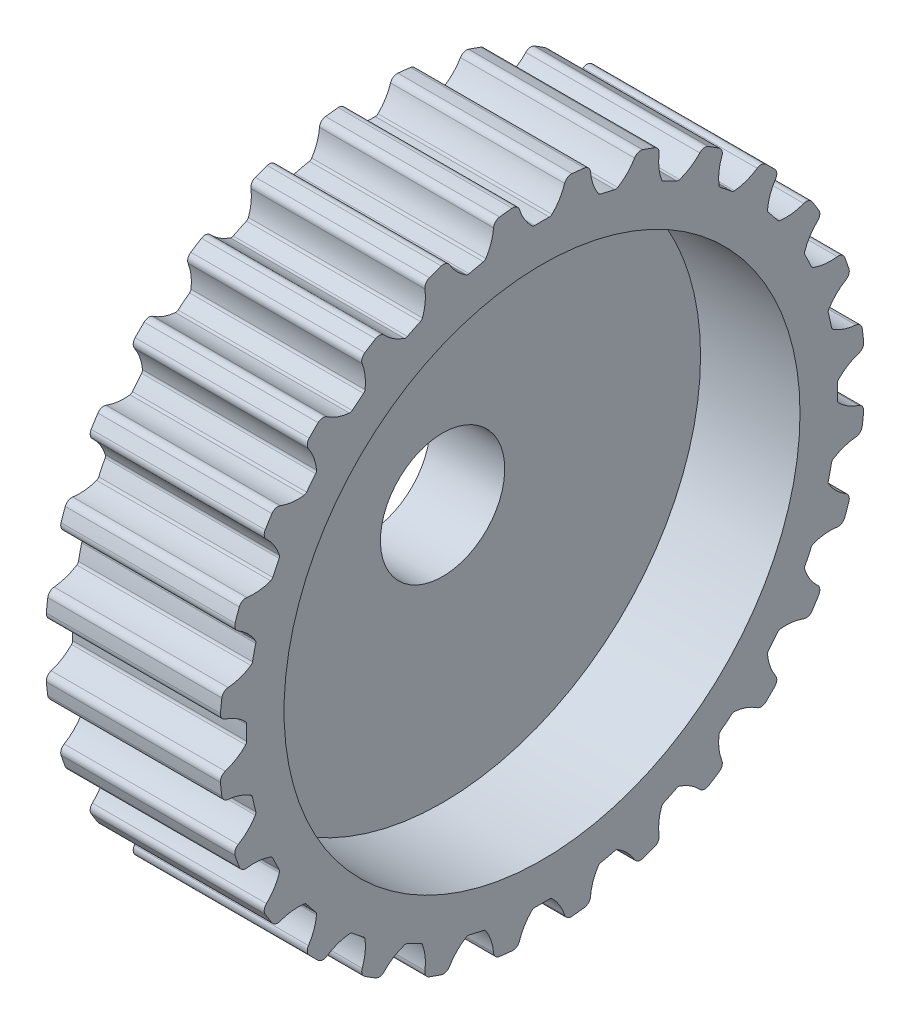
SolidWorks part; units mm, degrees
ref_plane "前视基准面" through (0, 0, 0) normal (0, 0, 1) x (1, 0, 0)
ref_plane "上视基准面" through (0, 0, 0) normal (0, 1, 0) x (1, 0, 0)
ref_plane "右视基准面" through (0, 0, 0) normal (1, 0, 0) x (0, 0, -1)
ref_plane "基准面1" through (0, 0, 0) normal (0, 0, 1) x (1, 0, 0)
sketch "草图1" plane through (0, 0, 0) normal (0, 0, 1) x (1, 0, 0)
  line L0 (0, 0) -> (0, 10)
  line L1 (0, 10) -> (1, 10)
  line L2 (1, 10) -> (1, 12.8583)
  line L3 (1, 12.8583) -> (0.4955, 14.7412)
  line L4 (0.4955, 14.7412) -> (1.4614, 15)
  line L5 (1.4614, 15) -> (2, 12.99)
  line L6 (2, 12.99) -> (9, 12.99)
  line L7 (9, 12.99) -> (9.5386, 15)
  line L8 (9.5386, 15) -> (10.5045, 14.7412)
  line L9 (10.5045, 14.7412) -> (10, 12.8583)
  line L10 (10, 12.8583) -> (10, 10)
  line L11 (10, 10) -> (11, 10)
  line L12 (11, 10) -> (11, 0)
  line L13 (11, 0) -> (0, 0)
  line L14 (11, 0) -> (0, 0) construction
revolve "旋转1" add sketch "草图1" angle 360 about L14 reverse direction yes
ref_plane "基准面2" through (0, 0, 0) normal (0, 0, 1) x (1, 0, 0)
hole_wizard "孔1" positions "草图3" profile "草图2" legacy
sketch "草图3" plane through (11, 0, 0) normal (1, 0, 0) x (0, 0, -1)
  point P0 (0, 0)
sketch "草图2" plane through (11, 0, 0) normal (0, 1, 0) x (0, 0, -1)
  line L0 (0, 0) -> (0, 11)
  line L1 (0, 11) -> (2.5, 11)
  line L2 (2.5, 11) -> (2.5, 0)
  line L3 (2.5, 0) -> (0, 0)
  line L4 (0, 110) -> (0, -10) construction
  dimension "直径" = 5
  dimension "深度" = 11
ref_plane "基准面3" through (2, 0, 0) normal (1, 0, 0) x (0, 0, -1)
sketch "草图4" plane through (2, 0, 0) normal (1, 0, 0) x (0, 0, -1)
  circle A0 centre (0, 0) radius 17.99
  arc A1 (-12.9343, 1.2013) -> (-12.7398, 0.9084) centre (-12.6555, 1.1754) ccw
  arc A2 (-12.7398, 0.9084) -> (-11.9188, 0.4022) centre (-13.3344, -0.975) cw
  arc A3 (-11.9188, 0.4022) -> (-11.8764, 0.2939) centre (-12.0263, 0.2976) cw
  arc A4 (-11.8764, 0.2939) -> (-11.8764, -0.2939) centre (0, 0) ccw
  arc A5 (-11.8764, -0.2939) -> (-11.9188, -0.4022) centre (-12.0263, -0.2976) cw
  arc A6 (-11.9188, -0.4022) -> (-12.7398, -0.9084) centre (-13.3344, 0.975) cw
  arc A7 (-12.7398, -0.9084) -> (-12.9343, -1.2013) centre (-12.6555, -1.1754) ccw
  arc A8 (-12.9343, -1.2013) -> (-12.8774, -1.707) centre (0, 0) ccw
  arc A9 (-12.8774, -1.707) -> (-12.6225, -1.9493) centre (-12.5998, -1.6702) ccw
  arc A10 (-12.6225, -1.9493) -> (-11.7095, -2.2601) centre (-12.7831, -3.9177) cw
  arc A11 (-11.7095, -2.2601) -> (-11.644, -2.3562) centre (-11.791, -2.386) cw
  arc A12 (-11.644, -2.3562) -> (-11.5132, -2.9293) centre (0, 0) ccw
  arc A13 (-11.5132, -2.9293) -> (-11.5305, -3.0443) centre (-11.6586, -2.9663) cw
  arc A14 (-11.5305, -3.0443) -> (-12.2183, -3.7205) centre (-13.217, -2.0166) cw
  arc A15 (-12.2183, -3.7205) -> (-12.3427, -4.0493) centre (-12.0767, -3.962) ccw
  arc A16 (-12.3427, -4.0493) -> (-12.1746, -4.5297) centre (0, 0) ccw
  arc A17 (-12.1746, -4.5297) -> (-11.8723, -4.7092) centre (-11.9122, -4.432) ccw
  arc A18 (-11.8723, -4.7092) -> (-10.913, -4.809) centre (-11.5908, -6.664) cw
  arc A19 (-10.913, -4.809) -> (-10.8278, -4.8882) centre (-10.9645, -4.9499) cw
  arc A20 (-10.8278, -4.8882) -> (-10.5727, -5.4178) centre (0, 0) ccw
  arc A21 (-10.5727, -5.4178) -> (-10.564, -5.5338) centre (-10.7062, -5.4862) cw
  arc A22 (-10.564, -5.5338) -> (-11.0841, -6.346) centre (-12.4369, -4.9071) cw
  arc A23 (-11.0841, -6.346) -> (-11.1322, -6.6943) centre (-10.8923, -6.55) ccw
  arc A24 (-11.1322, -6.6943) -> (-10.8615, -7.1252) centre (0, 0) ccw
  arc A25 (-10.8615, -7.1252) -> (-10.5268, -7.233) centre (-10.6273, -6.9716) ccw
  arc A26 (-10.5268, -7.233) -> (-9.5693, -7.1168) centre (-9.8174, -9.0761) cw
  arc A27 (-9.5693, -7.1168) -> (-9.4686, -7.175) centre (-9.5881, -7.2656) cw
  arc A28 (-9.4686, -7.175) -> (-9.1021, -7.6346) centre (0, 0) ccw
  arc A29 (-9.1021, -7.6346) -> (-9.0677, -7.7457) centre (-9.217, -7.731) cw
  arc A30 (-9.0677, -7.7457) -> (-9.394, -8.6534) centre (-11.0332, -7.5516) cw
  arc A31 (-9.394, -8.6534) -> (-9.3635, -9.0036) centre (-9.1617, -8.8096) ccw
  arc A32 (-9.3635, -9.0036) -> (-9.0036, -9.3635) centre (0, 0) ccw
  arc A33 (-9.0036, -9.3635) -> (-8.6534, -9.394) centre (-8.8096, -9.1617) ccw
  arc A34 (-8.6534, -9.394) -> (-7.7457, -9.0677) centre (-7.5516, -11.0332) cw
  arc A35 (-7.7457, -9.0677) -> (-7.6346, -9.1021) centre (-7.731, -9.217) cw
  arc A36 (-7.6346, -9.1021) -> (-7.175, -9.4686) centre (0, 0) ccw
  arc A37 (-7.175, -9.4686) -> (-7.1168, -9.5693) centre (-7.2656, -9.5881) cw
  arc A38 (-7.1168, -9.5693) -> (-7.233, -10.5268) centre (-9.0761, -9.8174) cw
  arc A39 (-7.233, -10.5268) -> (-7.1252, -10.8615) centre (-6.9716, -10.6273) ccw
  arc A40 (-7.1252, -10.8615) -> (-6.6943, -11.1322) centre (0, 0) ccw
  arc A41 (-6.6943, -11.1322) -> (-6.346, -11.0841) centre (-6.55, -10.8923) ccw
  arc A42 (-6.346, -11.0841) -> (-5.5338, -10.564) centre (-4.9071, -12.4369) cw
  arc A43 (-5.5338, -10.564) -> (-5.4178, -10.5727) centre (-5.4862, -10.7062) cw
  arc A44 (-5.4178, -10.5727) -> (-4.8882, -10.8278) centre (0, 0) ccw
  arc A45 (-4.8882, -10.8278) -> (-4.809, -10.913) centre (-4.9499, -10.9645) cw
  arc A46 (-4.809, -10.913) -> (-4.7092, -11.8723) centre (-6.664, -11.5908) cw
  arc A47 (-4.7092, -11.8723) -> (-4.5297, -12.1746) centre (-4.432, -11.9122) ccw
  arc A48 (-4.5297, -12.1746) -> (-4.0493, -12.3427) centre (0, 0) ccw
  arc A49 (-4.0493, -12.3427) -> (-3.7205, -12.2183) centre (-3.962, -12.0767) ccw
  arc A50 (-3.7205, -12.2183) -> (-3.0443, -11.5305) centre (-2.0166, -13.217) cw
  arc A51 (-3.0443, -11.5305) -> (-2.9293, -11.5132) centre (-2.9663, -11.6586) cw
  arc A52 (-2.9293, -11.5132) -> (-2.3562, -11.644) centre (0, 0) ccw
  arc A53 (-2.3562, -11.644) -> (-2.2601, -11.7095) centre (-2.386, -11.791) cw
  arc A54 (-2.2601, -11.7095) -> (-1.9493, -12.6225) centre (-3.9177, -12.7831) cw
  arc A55 (-1.9493, -12.6225) -> (-1.707, -12.8774) centre (-1.6702, -12.5998) ccw
  arc A56 (-1.707, -12.8774) -> (-1.2013, -12.9343) centre (0, 0) ccw
  arc A57 (-1.2013, -12.9343) -> (-0.9084, -12.7398) centre (-1.1754, -12.6555) ccw
  arc A58 (-0.9084, -12.7398) -> (-0.4022, -11.9188) centre (0.975, -13.3344) cw
  arc A59 (-0.4022, -11.9188) -> (-0.2939, -11.8764) centre (-0.2976, -12.0263) cw
  arc A60 (-0.2939, -11.8764) -> (0.2939, -11.8764) centre (0, 0) ccw
  arc A61 (0.2939, -11.8764) -> (0.4022, -11.9188) centre (0.2976, -12.0263) cw
  arc A62 (0.4022, -11.9188) -> (0.9084, -12.7398) centre (-0.975, -13.3344) cw
  arc A63 (0.9084, -12.7398) -> (1.2013, -12.9343) centre (1.1754, -12.6555) ccw
  arc A64 (1.2013, -12.9343) -> (1.707, -12.8774) centre (0, 0) ccw
  arc A65 (1.707, -12.8774) -> (1.9493, -12.6225) centre (1.6702, -12.5998) ccw
  arc A66 (1.9493, -12.6225) -> (2.2601, -11.7095) centre (3.9177, -12.7831) cw
  arc A67 (2.2601, -11.7095) -> (2.3562, -11.644) centre (2.386, -11.791) cw
  arc A68 (2.3562, -11.644) -> (2.9293, -11.5132) centre (0, 0) ccw
  arc A69 (2.9293, -11.5132) -> (3.0443, -11.5305) centre (2.9663, -11.6586) cw
  arc A70 (3.0443, -11.5305) -> (3.7205, -12.2183) centre (2.0166, -13.217) cw
  arc A71 (3.7205, -12.2183) -> (4.0493, -12.3427) centre (3.962, -12.0767) ccw
  arc A72 (4.0493, -12.3427) -> (4.5297, -12.1746) centre (0, 0) ccw
  arc A73 (4.5297, -12.1746) -> (4.7092, -11.8723) centre (4.432, -11.9122) ccw
  arc A74 (4.7092, -11.8723) -> (4.809, -10.913) centre (6.664, -11.5908) cw
  arc A75 (4.809, -10.913) -> (4.8882, -10.8278) centre (4.9499, -10.9645) cw
  arc A76 (4.8882, -10.8278) -> (5.4178, -10.5727) centre (0, 0) ccw
  arc A77 (5.4178, -10.5727) -> (5.5338, -10.564) centre (5.4862, -10.7062) cw
  arc A78 (5.5338, -10.564) -> (6.346, -11.0841) centre (4.9071, -12.4369) cw
  arc A79 (6.346, -11.0841) -> (6.6943, -11.1322) centre (6.55, -10.8923) ccw
  arc A80 (6.6943, -11.1322) -> (7.1252, -10.8615) centre (0, 0) ccw
  arc A81 (7.1252, -10.8615) -> (7.233, -10.5268) centre (6.9716, -10.6273) ccw
  arc A82 (7.233, -10.5268) -> (7.1168, -9.5693) centre (9.0761, -9.8174) cw
  arc A83 (7.1168, -9.5693) -> (7.175, -9.4686) centre (7.2656, -9.5881) cw
  arc A84 (7.175, -9.4686) -> (7.6346, -9.1021) centre (0, 0) ccw
  arc A85 (7.6346, -9.1021) -> (7.7457, -9.0677) centre (7.731, -9.217) cw
  arc A86 (7.7457, -9.0677) -> (8.6534, -9.394) centre (7.5516, -11.0332) cw
  arc A87 (8.6534, -9.394) -> (9.0036, -9.3635) centre (8.8096, -9.1617) ccw
  arc A88 (9.0036, -9.3635) -> (9.3635, -9.0036) centre (0, 0) ccw
  arc A89 (9.3635, -9.0036) -> (9.394, -8.6534) centre (9.1617, -8.8096) ccw
  arc A90 (9.394, -8.6534) -> (9.0677, -7.7457) centre (11.0332, -7.5516) cw
  arc A91 (9.0677, -7.7457) -> (9.1021, -7.6346) centre (9.217, -7.731) cw
  arc A92 (9.1021, -7.6346) -> (9.4686, -7.175) centre (0, 0) ccw
  arc A93 (9.4686, -7.175) -> (9.5693, -7.1168) centre (9.5881, -7.2656) cw
  arc A94 (9.5693, -7.1168) -> (10.5268, -7.233) centre (9.8174, -9.0761) cw
  arc A95 (10.5268, -7.233) -> (10.8615, -7.1252) centre (10.6273, -6.9716) ccw
  arc A96 (10.8615, -7.1252) -> (11.1322, -6.6943) centre (0, 0) ccw
  arc A97 (11.1322, -6.6943) -> (11.0841, -6.346) centre (10.8923, -6.55) ccw
  arc A98 (11.0841, -6.346) -> (10.564, -5.5338) centre (12.4369, -4.9071) cw
  arc A99 (10.564, -5.5338) -> (10.5727, -5.4178) centre (10.7062, -5.4862) cw
  arc A100 (10.5727, -5.4178) -> (10.8278, -4.8882) centre (0, 0) ccw
  arc A101 (10.8278, -4.8882) -> (10.913, -4.809) centre (10.9645, -4.9499) cw
  arc A102 (10.913, -4.809) -> (11.8723, -4.7092) centre (11.5908, -6.664) cw
  arc A103 (11.8723, -4.7092) -> (12.1746, -4.5297) centre (11.9122, -4.432) ccw
  arc A104 (12.1746, -4.5297) -> (12.3427, -4.0493) centre (0, 0) ccw
  arc A105 (12.3427, -4.0493) -> (12.2183, -3.7205) centre (12.0767, -3.962) ccw
  arc A106 (12.2183, -3.7205) -> (11.5305, -3.0443) centre (13.217, -2.0166) cw
  arc A107 (11.5305, -3.0443) -> (11.5132, -2.9293) centre (11.6586, -2.9663) cw
  arc A108 (11.5132, -2.9293) -> (11.644, -2.3562) centre (0, 0) ccw
  arc A109 (11.644, -2.3562) -> (11.7095, -2.2601) centre (11.791, -2.386) cw
  arc A110 (11.7095, -2.2601) -> (12.6225, -1.9493) centre (12.7831, -3.9177) cw
  arc A111 (12.6225, -1.9493) -> (12.8774, -1.707) centre (12.5998, -1.6702) ccw
  arc A112 (12.8774, -1.707) -> (12.9343, -1.2013) centre (0, 0) ccw
  arc A113 (12.9343, -1.2013) -> (12.7398, -0.9084) centre (12.6555, -1.1754) ccw
  arc A114 (12.7398, -0.9084) -> (11.9188, -0.4022) centre (13.3344, 0.975) cw
  arc A115 (11.9188, -0.4022) -> (11.8764, -0.2939) centre (12.0263, -0.2976) cw
  arc A116 (11.8764, -0.2939) -> (11.8764, 0.2939) centre (0, 0) ccw
  arc A117 (11.8764, 0.2939) -> (11.9188, 0.4022) centre (12.0263, 0.2976) cw
  arc A118 (11.9188, 0.4022) -> (12.7398, 0.9084) centre (13.3344, -0.975) cw
  arc A119 (12.7398, 0.9084) -> (12.9343, 1.2013) centre (12.6555, 1.1754) ccw
  arc A120 (12.9343, 1.2013) -> (12.8774, 1.707) centre (0, 0) ccw
  arc A121 (12.8774, 1.707) -> (12.6225, 1.9493) centre (12.5998, 1.6702) ccw
  arc A122 (12.6225, 1.9493) -> (11.7095, 2.2601) centre (12.7831, 3.9177) cw
  arc A123 (11.7095, 2.2601) -> (11.644, 2.3562) centre (11.791, 2.386) cw
  arc A124 (11.644, 2.3562) -> (11.5132, 2.9293) centre (0, 0) ccw
  arc A125 (11.5132, 2.9293) -> (11.5305, 3.0443) centre (11.6586, 2.9663) cw
  arc A126 (11.5305, 3.0443) -> (12.2183, 3.7205) centre (13.217, 2.0166) cw
  arc A127 (12.2183, 3.7205) -> (12.3427, 4.0493) centre (12.0767, 3.962) ccw
  arc A128 (12.3427, 4.0493) -> (12.1746, 4.5297) centre (0, 0) ccw
  arc A129 (12.1746, 4.5297) -> (11.8723, 4.7092) centre (11.9122, 4.432) ccw
  arc A130 (11.8723, 4.7092) -> (10.913, 4.809) centre (11.5908, 6.664) cw
  arc A131 (10.913, 4.809) -> (10.8278, 4.8882) centre (10.9645, 4.9499) cw
  arc A132 (10.8278, 4.8882) -> (10.5727, 5.4178) centre (0, 0) ccw
  arc A133 (10.5727, 5.4178) -> (10.564, 5.5338) centre (10.7062, 5.4862) cw
  arc A134 (10.564, 5.5338) -> (11.0841, 6.346) centre (12.4369, 4.9071) cw
  arc A135 (11.0841, 6.346) -> (11.1322, 6.6943) centre (10.8923, 6.55) ccw
  arc A136 (11.1322, 6.6943) -> (10.8615, 7.1252) centre (0, 0) ccw
  arc A137 (10.8615, 7.1252) -> (10.5268, 7.233) centre (10.6273, 6.9716) ccw
  arc A138 (10.5268, 7.233) -> (9.5693, 7.1168) centre (9.8174, 9.0761) cw
  arc A139 (9.5693, 7.1168) -> (9.4686, 7.175) centre (9.5881, 7.2656) cw
  arc A140 (9.4686, 7.175) -> (9.1021, 7.6346) centre (0, 0) ccw
  arc A141 (9.1021, 7.6346) -> (9.0677, 7.7457) centre (9.217, 7.731) cw
  arc A142 (9.0677, 7.7457) -> (9.394, 8.6534) centre (11.0332, 7.5516) cw
  arc A143 (9.394, 8.6534) -> (9.3635, 9.0036) centre (9.1617, 8.8096) ccw
  arc A144 (9.3635, 9.0036) -> (9.0036, 9.3635) centre (0, 0) ccw
  arc A145 (9.0036, 9.3635) -> (8.6534, 9.394) centre (8.8096, 9.1617) ccw
  arc A146 (8.6534, 9.394) -> (7.7457, 9.0677) centre (7.5516, 11.0332) cw
  arc A147 (7.7457, 9.0677) -> (7.6346, 9.1021) centre (7.731, 9.217) cw
  arc A148 (7.6346, 9.1021) -> (7.175, 9.4686) centre (0, 0) ccw
  arc A149 (7.175, 9.4686) -> (7.1168, 9.5693) centre (7.2656, 9.5881) cw
  arc A150 (7.1168, 9.5693) -> (7.233, 10.5268) centre (9.0761, 9.8174) cw
  arc A151 (7.233, 10.5268) -> (7.1252, 10.8615) centre (6.9716, 10.6273) ccw
  arc A152 (7.1252, 10.8615) -> (6.6943, 11.1322) centre (0, 0) ccw
  arc A153 (6.6943, 11.1322) -> (6.346, 11.0841) centre (6.55, 10.8923) ccw
  arc A154 (6.346, 11.0841) -> (5.5338, 10.564) centre (4.9071, 12.4369) cw
  arc A155 (5.5338, 10.564) -> (5.4178, 10.5727) centre (5.4862, 10.7062) cw
  arc A156 (5.4178, 10.5727) -> (4.8882, 10.8278) centre (0, 0) ccw
  arc A157 (4.8882, 10.8278) -> (4.809, 10.913) centre (4.9499, 10.9645) cw
  arc A158 (4.809, 10.913) -> (4.7092, 11.8723) centre (6.664, 11.5908) cw
  arc A159 (4.7092, 11.8723) -> (4.5297, 12.1746) centre (4.432, 11.9122) ccw
  arc A160 (4.5297, 12.1746) -> (4.0493, 12.3427) centre (0, 0) ccw
  arc A161 (4.0493, 12.3427) -> (3.7205, 12.2183) centre (3.962, 12.0767) ccw
  arc A162 (3.7205, 12.2183) -> (3.0443, 11.5305) centre (2.0166, 13.217) cw
  arc A163 (3.0443, 11.5305) -> (2.9293, 11.5132) centre (2.9663, 11.6586) cw
  arc A164 (2.9293, 11.5132) -> (2.3562, 11.644) centre (0, 0) ccw
  arc A165 (2.3562, 11.644) -> (2.2601, 11.7095) centre (2.386, 11.791) cw
  arc A166 (2.2601, 11.7095) -> (1.9493, 12.6225) centre (3.9177, 12.7831) cw
  arc A167 (1.9493, 12.6225) -> (1.707, 12.8774) centre (1.6702, 12.5998) ccw
  arc A168 (1.707, 12.8774) -> (1.2013, 12.9343) centre (0, 0) ccw
  arc A169 (1.2013, 12.9343) -> (0.9084, 12.7398) centre (1.1754, 12.6555) ccw
  arc A170 (0.9084, 12.7398) -> (0.4022, 11.9188) centre (-0.975, 13.3344) cw
  arc A171 (0.4022, 11.9188) -> (0.2939, 11.8764) centre (0.2976, 12.0263) cw
  arc A172 (0.2939, 11.8764) -> (-0.2939, 11.8764) centre (0, 0) ccw
  arc A173 (-0.2939, 11.8764) -> (-0.4022, 11.9188) centre (-0.2976, 12.0263) cw
  arc A174 (-0.4022, 11.9188) -> (-0.9084, 12.7398) centre (0.975, 13.3344) cw
  arc A175 (-0.9084, 12.7398) -> (-1.2013, 12.9343) centre (-1.1754, 12.6555) ccw
  arc A176 (-1.2013, 12.9343) -> (-1.707, 12.8774) centre (0, 0) ccw
  arc A177 (-1.707, 12.8774) -> (-1.9493, 12.6225) centre (-1.6702, 12.5998) ccw
  arc A178 (-1.9493, 12.6225) -> (-2.2601, 11.7095) centre (-3.9177, 12.7831) cw
  arc A179 (-2.2601, 11.7095) -> (-2.3562, 11.644) centre (-2.386, 11.791) cw
  arc A180 (-2.3562, 11.644) -> (-2.9293, 11.5132) centre (0, 0) ccw
  arc A181 (-2.9293, 11.5132) -> (-3.0443, 11.5305) centre (-2.9663, 11.6586) cw
  arc A182 (-3.0443, 11.5305) -> (-3.7205, 12.2183) centre (-2.0166, 13.217) cw
  arc A183 (-3.7205, 12.2183) -> (-4.0493, 12.3427) centre (-3.962, 12.0767) ccw
  arc A184 (-4.0493, 12.3427) -> (-4.5297, 12.1746) centre (0, 0) ccw
  arc A185 (-4.5297, 12.1746) -> (-4.7092, 11.8723) centre (-4.432, 11.9122) ccw
  arc A186 (-4.7092, 11.8723) -> (-4.809, 10.913) centre (-6.664, 11.5908) cw
  arc A187 (-4.809, 10.913) -> (-4.8882, 10.8278) centre (-4.9499, 10.9645) cw
  arc A188 (-4.8882, 10.8278) -> (-5.4178, 10.5727) centre (0, 0) ccw
  arc A189 (-5.4178, 10.5727) -> (-5.5338, 10.564) centre (-5.4862, 10.7062) cw
  arc A190 (-5.5338, 10.564) -> (-6.346, 11.0841) centre (-4.9071, 12.4369) cw
  arc A191 (-6.346, 11.0841) -> (-6.6943, 11.1322) centre (-6.55, 10.8923) ccw
  arc A192 (-6.6943, 11.1322) -> (-7.1252, 10.8615) centre (0, 0) ccw
  arc A193 (-7.1252, 10.8615) -> (-7.233, 10.5268) centre (-6.9716, 10.6273) ccw
  arc A194 (-7.233, 10.5268) -> (-7.1168, 9.5693) centre (-9.0761, 9.8174) cw
  arc A195 (-7.1168, 9.5693) -> (-7.175, 9.4686) centre (-7.2656, 9.5881) cw
  arc A196 (-7.175, 9.4686) -> (-7.6346, 9.1021) centre (0, 0) ccw
  arc A197 (-7.6346, 9.1021) -> (-7.7457, 9.0677) centre (-7.731, 9.217) cw
  arc A198 (-7.7457, 9.0677) -> (-8.6534, 9.394) centre (-7.5516, 11.0332) cw
  arc A199 (-8.6534, 9.394) -> (-9.0036, 9.3635) centre (-8.8096, 9.1617) ccw
  arc A200 (-9.0036, 9.3635) -> (-9.3635, 9.0036) centre (0, 0) ccw
  arc A201 (-9.3635, 9.0036) -> (-9.394, 8.6534) centre (-9.1617, 8.8096) ccw
  arc A202 (-9.394, 8.6534) -> (-9.0677, 7.7457) centre (-11.0332, 7.5516) cw
  arc A203 (-9.0677, 7.7457) -> (-9.1021, 7.6346) centre (-9.217, 7.731) cw
  arc A204 (-9.1021, 7.6346) -> (-9.4686, 7.175) centre (0, 0) ccw
  arc A205 (-9.4686, 7.175) -> (-9.5693, 7.1168) centre (-9.5881, 7.2656) cw
  arc A206 (-9.5693, 7.1168) -> (-10.5268, 7.233) centre (-9.8174, 9.0761) cw
  arc A207 (-10.5268, 7.233) -> (-10.8615, 7.1252) centre (-10.6273, 6.9716) ccw
  arc A208 (-10.8615, 7.1252) -> (-11.1322, 6.6943) centre (0, 0) ccw
  arc A209 (-11.1322, 6.6943) -> (-11.0841, 6.346) centre (-10.8923, 6.55) ccw
  arc A210 (-11.0841, 6.346) -> (-10.564, 5.5338) centre (-12.4369, 4.9071) cw
  arc A211 (-10.564, 5.5338) -> (-10.5727, 5.4178) centre (-10.7062, 5.4862) cw
  arc A212 (-10.5727, 5.4178) -> (-10.8278, 4.8882) centre (0, 0) ccw
  arc A213 (-10.8278, 4.8882) -> (-10.913, 4.809) centre (-10.9645, 4.9499) cw
  arc A214 (-10.913, 4.809) -> (-11.8723, 4.7092) centre (-11.5908, 6.664) cw
  arc A215 (-11.8723, 4.7092) -> (-12.1746, 4.5297) centre (-11.9122, 4.432) ccw
  arc A216 (-12.1746, 4.5297) -> (-12.3427, 4.0493) centre (0, 0) ccw
  arc A217 (-12.3427, 4.0493) -> (-12.2183, 3.7205) centre (-12.0767, 3.962) ccw
  arc A218 (-12.2183, 3.7205) -> (-11.5305, 3.0443) centre (-13.217, 2.0166) cw
  arc A219 (-11.5305, 3.0443) -> (-11.5132, 2.9293) centre (-11.6586, 2.9663) cw
  arc A220 (-11.5132, 2.9293) -> (-11.644, 2.3562) centre (0, 0) ccw
  arc A221 (-11.644, 2.3562) -> (-11.7095, 2.2601) centre (-11.791, 2.386) cw
  arc A222 (-11.7095, 2.2601) -> (-12.6225, 1.9493) centre (-12.7831, 3.9177) cw
  arc A223 (-12.6225, 1.9493) -> (-12.8774, 1.707) centre (-12.5998, 1.6702) ccw
  arc A224 (-12.8774, 1.707) -> (-12.9343, 1.2013) centre (0, 0) ccw
extrude "切除-拉伸1" cut sketch "草图4" along normal blind 7
ref_plane "基准面4" through (0, 0, 0) normal (0, 0, 1) x (1, 0, 0)
ref_plane "基准面5" through (5.5, 0, 0) normal (1, 0, 0) x (0, 0, -1)
ref_plane "to_belt XY" through (5.5, 0, 0) normal (-1, 0, 0) x (0, 0, 1)
ref_plane "to_belt XZ" through (0, 0, 0) normal (0, 1, 0) x (1, 0, 0)
ref_plane "to_belt YZ" through (0, 0, 0) normal (0, 0, -1) x (-1, 0, 0)
ref_axis "to_belt X" through (5.5, 0, 80.9) along (0, 0, -1)
ref_axis "to_belt Y" through (5.5, 50, 0) along (0, -1, 0)
ref_axis "to_belt Z" through (-80.9, 0, 0) along (1, 0, 0)
sketch3d "to_belt"
  point P0 (5.5, 0, 0)
sketch "草图5" plane through (0, 0, 0) normal (0, 0, 1) x (1, 0, 0)
  line L1 (-10.5886, 18.7406) -> (2, 18.7406)
  line L2 (-10.5886, 18.7406) -> (-10.5886, -21.2299)
  line L3 (-10.5886, -21.2299) -> (2, -21.2299)
  line L4 (2, 18.7406) -> (2, -21.2299)
  line L5 (9, -22.5101) -> (34.675, -22.5101)
  line L6 (9, -22.5101) -> (9, 27.6308)
  line L7 (9, 27.6308) -> (34.675, 27.6308)
  line L8 (34.675, -22.5101) -> (34.675, 27.6308)
extrude "切除-拉伸2" cut sketch "草图5" against normal through all both and the other way through all
sketch "草图6" plane through (9, 0, 0) normal (1, 0, 0) x (0, 0, -1)
  circle A0 centre (0, 0) radius 10.375
  dimension "D1" = 20.75
extrude "切除-拉伸3" cut sketch "草图6" against normal offset from surface (4 mm away) 3 up to face at (2, 0, 0)
